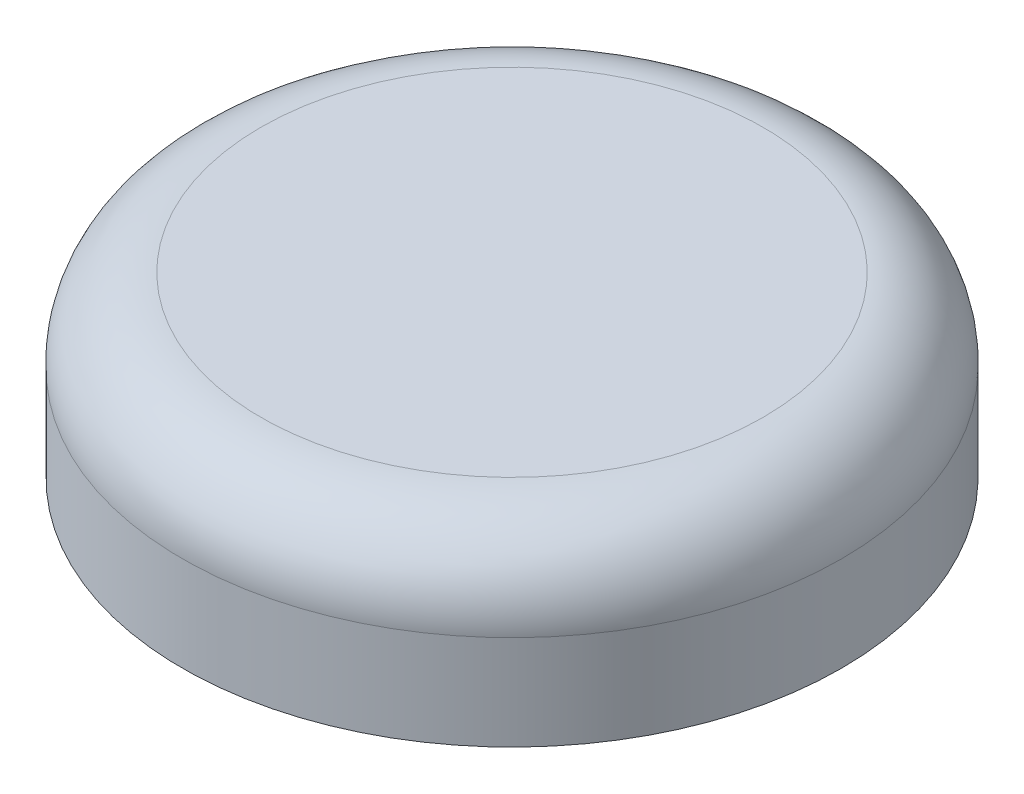
SolidWorks part; units mm, degrees
ref_plane "Front Plane" through (0, 0, 0) normal (0, 0, 1) x (1, 0, 0)
ref_plane "Top Plane" through (0, 0, 0) normal (0, 1, 0) x (1, 0, 0)
ref_plane "Right Plane" through (0, 0, 0) normal (1, 0, 0) x (0, 0, -1)
sketch "Sketch1" plane through (0, 0, 0) normal (0, 0, 1) x (1, 0, 0)
  line L0 (0, -1000) -> (0, 49000) construction
  line L1 (0, 22.4251) -> (-48.0306, 22.4251)
  line L2 (-63, 6.4668) -> (-63, -11.6477)
  line L3 (-63, -11.6477) -> (-60.5, -11.6477)
  line L4 (-60.5, -11.6477) -> (-60.5, 6.6523)
  line L5 (-60.5, 6.6523) -> (-59.0035, 6.6523)
  line L6 (-48.0306, 18.4251) -> (0, 18.4251)
  line L14 (0, 22.4251) -> (0, 18.4251)
  arc A0 (-48.0306, 22.4251) -> (-63, 6.4668) centre (-48.0306, 7.4251) ccw
  arc A1 (-48.0306, 18.4251) -> (-59.0035, 6.6523) centre (-48.0306, 7.4251) ccw
  dimension "D1" = 15
  dimension "D2" = 4
  dimension "D3" = 2.5
  dimension "D5" = 60.5
  dimension "D6" = 18.3
revolve "Revolve1" add sketch "Sketch1" angle 360 about L0
thread "Thread1" pitch 1.5 method cut profile "Thread Profile1" start angle 0, offset 0, length 20, pitch 1.5, diameter 121
ref_plane "Plane1" through (-60.5, 6.6523, 0) normal (0, 0, 1) x (-1, 0, 0)
sketch "Thread Profile1" plane through (-60.5, 6.6523, 0) normal (0, 0, 1) x (-1, 0, 0)
  line L0 (0, 0) -> (0, 1.5) construction
  line L1 (0, 0) -> (0.8119, 0.4687)
  line L2 (0.8119, 0.4687) -> (0.8119, 0.6562)
  line L3 (0.8119, 0.6562) -> (0, 1.125)
  line L4 (0.8119, 0.5625) -> (0, 0.5625) construction
  line L11 (0, 0) -> (0, 1.125)
  point P2 (0, 0)
  dimension "Pitch" = 1.5
  dimension "Profile_Angle" = 60
  dimension "Profile_Land" = 0.1875
  dimension "Profile_Height" = 0.8119
sketch "Sketch2" plane through (0, 22.4251, 0) normal (0, 1, 0) x (1, 0, 0)
  circle A0 centre (0, 32) radius 5
  circle A1 centre (0, 32) radius 6
  circle A2 centre (-32, 0) radius 4
  circle A3 centre (-32, 0) radius 5
  circle A4 centre (0, -32) radius 3.4163
  circle A5 centre (0, -32) radius 4
  dimension "D2" = 10
  dimension "D3" = 12
  dimension "D4" = 8
  dimension "D5" = 10
  dimension "D8" = 8
  dimension "D1" = 32
  dimension "D6" = 32
  dimension "D7" = 32
extrude "Boss-Extrude1" [suppressed] add sketch "Sketch2" along normal blind 5
sketch "Sketch3" [suppressed] plane through (0, 22.4251, 0) normal (0, 1, 0) x (1, 0, 0)
  circle A0 centre (0, 32) radius 5
  circle A1 centre (-32, 0) radius 4
  circle A2 centre (0, -32) radius 3.45
  dimension "D1" = 8
  dimension "D2" = 6.9
extrude "Cut-Extrude1" [suppressed] cut sketch "Sketch3" against normal blind 10
